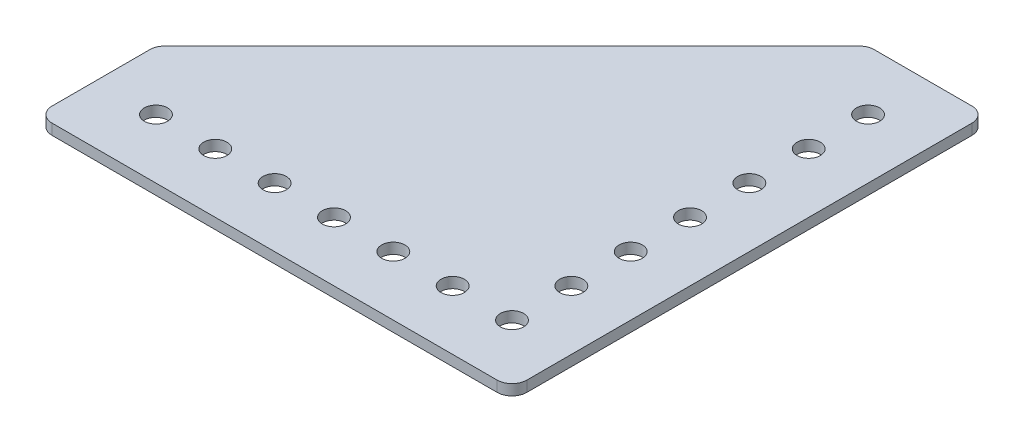
SolidWorks part; units mm, degrees
ref_plane "Front Plane" through (0, 0, 0) normal (0, 0, 1) x (1, 0, 0)
ref_plane "Top Plane" through (0, 0, 0) normal (0, 1, 0) x (1, 0, 0)
ref_plane "Right Plane" through (0, 0, 0) normal (1, 0, 0) x (0, 0, -1)
sketch "Sketch1" plane through (0, 0, 0) normal (0, 1, 0) x (1, 0, 0)
  line L0 (0, 0) -> (0, 101.6)
  line L1 (0, 101.6) -> (-25.4, 101.6)
  line L2 (-25.4, 101.6) -> (-101.6, 25.4)
  line L3 (-101.6, 25.4) -> (-101.6, 0)
  line L4 (-101.6, 0) -> (0, 0)
  circle A0 centre (-12.7, 12.7) radius 2.4892
  circle A1 centre (-25.4, 12.7) radius 2.4892
  circle A2 centre (-38.1, 12.7) radius 2.4892
  circle A3 centre (-50.8, 12.7) radius 2.4892
  circle A4 centre (-63.5, 12.7) radius 2.4892
  circle A5 centre (-12.7, 25.4) radius 2.4892
  circle A6 centre (-12.7, 38.1) radius 2.4892
  circle A7 centre (-12.7, 50.8) radius 2.4892
  circle A8 centre (-12.7, 63.5) radius 2.4892
  circle A9 centre (-76.2, 12.7) radius 2.4892
  circle A10 centre (-88.9, 12.7) radius 2.4892
  circle A11 centre (-12.7, 88.9) radius 2.4892
  circle A13 centre (-12.7, 76.2) radius 2.4892
  dimension "D4" = 12.7
  dimension "D5" = 12.7
  dimension "D1" = 101.6
  dimension "D2" = 25.4
  dimension "D3" = 101.6
  dimension "D10" = 25.4
  dimension "D6" = 7
  dimension "D7" = 7
extrude "Boss-Extrude2" add sketch "Sketch1" along normal mid plane 2.286
fillet "Fillet1" radius 3.175 2 edges at (0, 0, 0) (-101.6, 0, 0)
fillet "Fillet2" radius 3.175 3 edges at (-101.6, 0, -25.4) (0, 0, -101.6) (-25.4, 0, -101.6)
